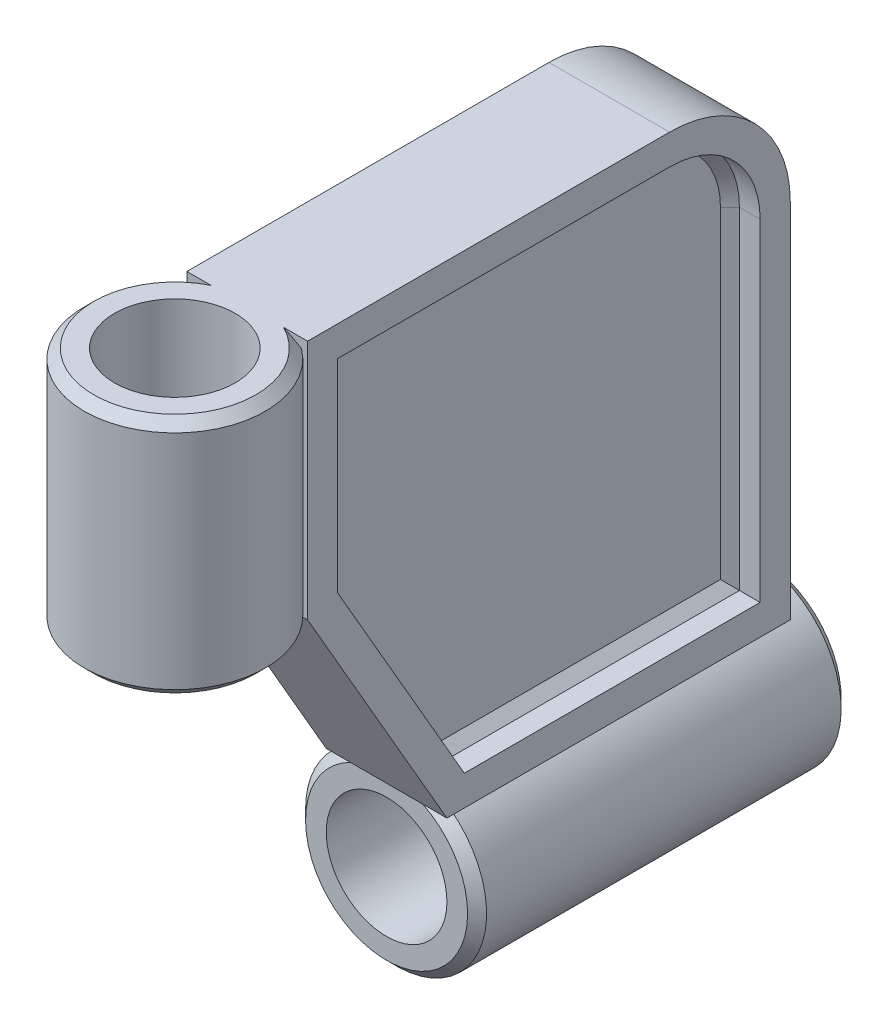
SolidWorks part; units mm, degrees
ref_plane "Front Plane" through (0, 0, 0) normal (1, 0, 0) x (0, 1, 0)
ref_plane "Top Plane" through (0, 0, 0) normal (0, 0, 1) x (0, 1, 0)
ref_plane "Right Plane" through (0, 0, 0) normal (0, 1, 0) x (-1, 0, 0)
sketch "Sketch1" plane through (0, 0, 0) normal (1, 0, 0) x (0, 1, 0)
  line L0 (-25.4, 10.7353) -> (0, 25.4)
  line L1 (-25.4, -25.4) -> (25.4, -25.4)
  line L2 (-25.4, -25.4) -> (-25.4, 10.7353)
  line L3 (0, 25.4) -> (25.4, 25.4)
  line L4 (25.4, -25.4) -> (25.4, 25.4)
  line L5 (0, -55) -> (0, 55) construction
  line L6 (55, 0) -> (-55, 0) construction
  point P0 (0, 0)
  point P10 (25.4, 0)
  dimension "D1" = 50.8
  dimension "D2" = 50.8
  dimension "D3" = 30
  dimension "D4" = 25.4
extrude "Boss-Extrude1" add sketch "Sketch1" along normal mid plane 12.7
fillet "Fillet1" radius 12.7 1 edges at (0, 25.4, -25.4)
sketch "Sketch3" plane through (6.35, 0, 0) normal (1, 0, 0) x (0, 1, 0)
  line L10 (-22.225, -22.225) -> (12.7, -22.225)
  line L11 (22.225, -12.7) -> (22.225, 22.225)
  line L12 (22.225, 22.225) -> (0.8507, 22.225)
  line L13 (0.8507, 22.225) -> (-22.225, 8.9022)
  line L14 (-22.225, 8.9022) -> (-22.225, -22.225)
  line L15 (-22.225, -22.225) -> (12.7, -22.225)
  line L16 (22.225, -12.7) -> (22.225, 22.225)
  line L17 (22.225, 22.225) -> (0.8507, 22.225)
  line L18 (0.8507, 22.225) -> (-22.225, 8.9022)
  line L19 (-22.225, 8.9022) -> (-22.225, -22.225)
  arc A2 (12.7, -22.225) -> (22.225, -12.7) centre (12.7, -12.7) ccw
  arc A3 (12.7, -22.225) -> (22.225, -12.7) centre (12.7, -12.7) ccw
  dimension "D1" = 3.175
extrude "Cut-Extrude2" cut sketch "Sketch3" against normal blind 3.175
mirror "Mirror1" about plane through (0, 0, 0) normal (1, 0, 0) of "Cut-Extrude2"
sketch "Sketch4" plane through (0, 0, -25.4) normal (0, 0, -1) x (1, 0, 0)
  line L0 (0, -27.94) -> (0, 27.94) construction
  line L1 (6.35, -25.4) -> (-6.35, -25.4) construction
  circle A0 centre (0, 33.02) radius 9.525
  circle A1 centre (0, 33.02) radius 6.35
  dimension "D1" = 19.05
  dimension "D2" = 12.7
  dimension "D3" = 58.42
extrude "Boss-Extrude2" add sketch "Sketch4" against normal up to vertex (36.1353 mm away) and the other way blind 3.175 up to point (6.35, -25.4, 10.7353)
sketch "Sketch5" plane through (0, 25.4, 0) normal (0, 1, 0) x (-1, 0, 0)
  line L0 (0, 29.6863) -> (0, -29.6863) construction
  line L1 (-5.715, -25.4) -> (5.715, -25.4) construction
  circle A0 centre (0, 33.02) radius 9.525
  circle A1 centre (0, 33.02) radius 6.35
  dimension "D1" = 19.05
  dimension "D2" = 12.7
  dimension "D3" = 58.42
extrude "Boss-Extrude3" add sketch "Sketch5" against normal up to surface (25.4 mm away) up to plane "Right Plane"
chamfer "Chamfer2" distance 1 angle 45 4 edges at (0, 0, 42.545) (0, -42.545, 10.7353) (0, -23.495, -28.575) (0, 25.4, 42.545)
sketch "Sketch6" plane through (0, 0, 0) normal (1, 0, 0) x (0, 1, 0)
  line L0 (-26.67, 10.7353) -> (-39.37, 10.7353) construction
  line L1 (-26.67, 10.7353) -> (-39.37, 10.7353) construction
  line L2 (0, 39.37) -> (0, 26.67) construction
  line L3 (0, 39.37) -> (0, 26.67) construction
  line L4 (-20.32, 33.02) -> (0, 33.02)
  line L5 (-33.02, 20.32) -> (-33.02, 10.7353)
  arc A0 (-33.02, 20.32) -> (-20.32, 33.02) centre (-20.32, 20.32) cw
  point P6 (-33.02, 10.7353)
  point P9 (0, 33.02)
  dimension "D1" = 12.7
sketch "Sketch7" plane through (0, 0, 0) normal (0, -1, 0) x (1, 0, 0)
  line L0 (-8.525, 33.02) -> (-6.35, 33.02)
  line L1 (6.35, 33.02) -> (8.525, 33.02)
  line L2 (0, 39.37) -> (0, 26.67) construction
  circle A0 centre (0, 33.02) radius 6.35 construction
  arc A4 (-6.35, 33.02) -> (6.35, 33.02) centre (0, 33.02) ccw
  arc A5 (-8.525, 33.02) -> (8.525, 33.02) centre (0, 33.02) ccw
  arc A6 (3.8225, 25.4) -> (-3.8225, 25.4) centre (0, 33.02) ccw construction
chamfer "Chamfer4" distance 1 angle 45 12 edges at (-3.175, -4.7625, -22.225) (-3.175, 19.4352, -19.4352) (-3.175, 22.225, 4.7625) (-3.175, 11.5379, 22.225) (-3.175, -10.6871, 15.5636) (-3.175, -22.225, -6.6614) (3.175, -10.6871, 15.5636) (3.175, 11.5379, 22.225) (3.175, 22.225, 4.7625) (3.175, 19.4352, -19.4352) (3.175, -4.7625, -22.225) (3.175, -22.225, -6.6614)
